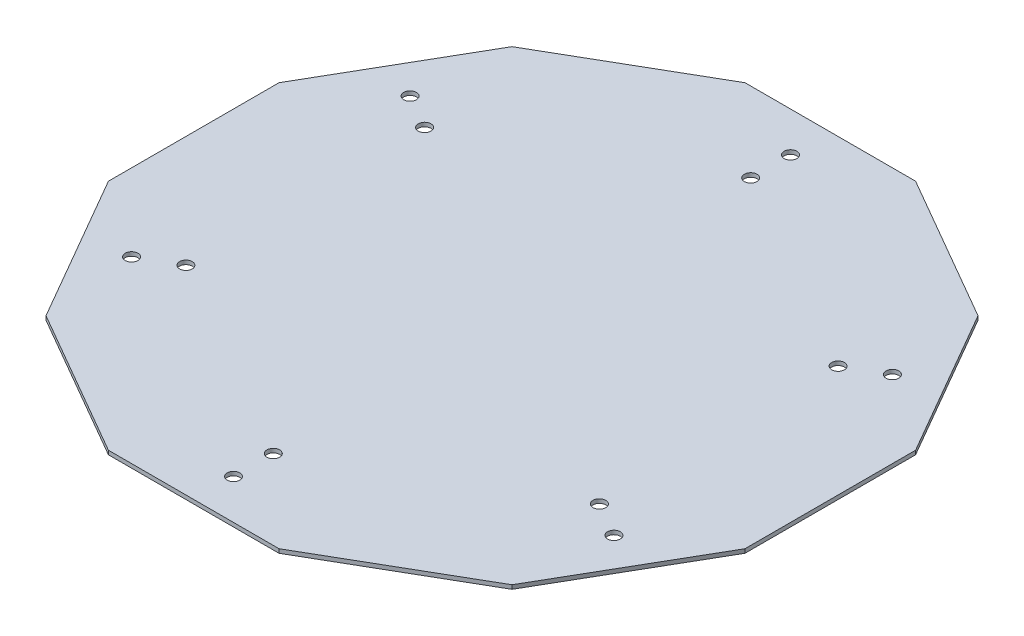
SolidWorks part; units mm, degrees
ref_plane "正面" through (0, 0, 0) normal (0, 0, 1) x (1, 0, 0)
ref_plane "平面" through (0, 0, 0) normal (0, 1, 0) x (1, 0, 0)
ref_plane "右側面" through (0, 0, 0) normal (1, 0, 0) x (0, 0, -1)
other "重心"
sketch "ｽｹｯﾁ8" plane through (0, 0, 0) normal (0, 1, 0) x (1, 0, 0)
  line L0 (-80, -21.4359) -> (-58.5641, -58.5641)
  line L1 (80, 21.4359) -> (58.5641, 58.5641)
  line L2 (58.5641, 58.5641) -> (21.4359, 80)
  line L3 (21.4359, 80) -> (-21.4359, 80)
  line L4 (-21.4359, 80) -> (-58.5641, 58.5641)
  line L5 (-58.5641, 58.5641) -> (-80, 21.4359)
  line L6 (-80, 21.4359) -> (-80, -21.4359)
  line L7 (-58.5641, -58.5641) -> (-21.4359, -80)
  line L8 (-21.4359, -80) -> (21.4359, -80)
  line L9 (21.4359, -80) -> (58.5641, -58.5641)
  line L10 (58.5641, -58.5641) -> (80, -21.4359)
  line L11 (80, -21.4359) -> (80, 21.4359)
  circle A0 centre (0, 0) radius 80 construction
extrude "ﾎﾞｽ - 押し出し2" add sketch "ｽｹｯﾁ8" along normal blind 1
sketch "ｽｹｯﾁ9" plane through (0, 1, 0) normal (0, 1, 0) x (1, 0, 0)
  circle A0 centre (-60.6218, 35) radius 1.6
extrude "ｶｯﾄ - 押し出し5" cut sketch "ｽｹｯﾁ9" against normal blind 1
sketch "ｽｹｯﾁ10" plane through (0, 1, 0) normal (0, 1, 0) x (1, 0, 0)
  circle A0 centre (-51.9615, 30) radius 1.6
extrude "ｶｯﾄ - 押し出し6" cut sketch "ｽｹｯﾁ10" against normal blind 1
sketch "ｽｹｯﾁ11" plane through (0, 1, 0) normal (0, 1, 0) x (1, 0, 0)
  circle A0 centre (60.6218, -35) radius 1.6
extrude "ｶｯﾄ - 押し出し7" cut sketch "ｽｹｯﾁ11" against normal blind 1
sketch "ｽｹｯﾁ12" plane through (0, 1, 0) normal (0, 1, 0) x (1, 0, 0)
  circle A0 centre (51.9615, -30) radius 1.6
extrude "ｶｯﾄ - 押し出し8" cut sketch "ｽｹｯﾁ12" against normal blind 1
sketch "ｽｹｯﾁ16" plane through (0, 1, 0) normal (0, 1, 0) x (1, 0, 0)
  circle A0 centre (60.6218, 35) radius 1.6
extrude "ｶｯﾄ - 押し出し9" cut sketch "ｽｹｯﾁ16" against normal blind 1
sketch "ｽｹｯﾁ17" plane through (0, 1, 0) normal (0, 1, 0) x (1, 0, 0)
  circle A0 centre (51.9615, 30) radius 1.6
extrude "ｶｯﾄ - 押し出し10" cut sketch "ｽｹｯﾁ17" against normal blind 1
sketch "ｽｹｯﾁ18" plane through (0, 1, 0) normal (0, 1, 0) x (1, 0, 0)
  circle A0 centre (-60.6218, -35) radius 1.6
extrude "ｶｯﾄ - 押し出し11" cut sketch "ｽｹｯﾁ18" against normal blind 1
sketch "ｽｹｯﾁ19" plane through (0, 1, 0) normal (0, 1, 0) x (1, 0, 0)
  circle A0 centre (-51.9615, -30) radius 1.6
extrude "ｶｯﾄ - 押し出し12" cut sketch "ｽｹｯﾁ19" against normal blind 1
sketch "ｽｹｯﾁ20" plane through (0, 1, 0) normal (0, 1, 0) x (1, 0, 0)
  circle A0 centre (0, 70) radius 1.6
extrude "ｶｯﾄ - 押し出し13" cut sketch "ｽｹｯﾁ20" against normal blind 1
sketch "ｽｹｯﾁ21" plane through (0, 1, 0) normal (0, 1, 0) x (1, 0, 0)
  circle A0 centre (0, 60) radius 1.6
extrude "ｶｯﾄ - 押し出し14" cut sketch "ｽｹｯﾁ21" against normal blind 1
sketch "ｽｹｯﾁ22" plane through (0, 1, 0) normal (0, 1, 0) x (1, 0, 0)
  circle A0 centre (0, -70) radius 1.6
extrude "ｶｯﾄ - 押し出し15" cut sketch "ｽｹｯﾁ22" against normal blind 1
sketch "ｽｹｯﾁ23" plane through (0, 1, 0) normal (0, 1, 0) x (1, 0, 0)
  circle A0 centre (0, -60) radius 1.6
extrude "ｶｯﾄ - 押し出し16" cut sketch "ｽｹｯﾁ23" against normal blind 1
